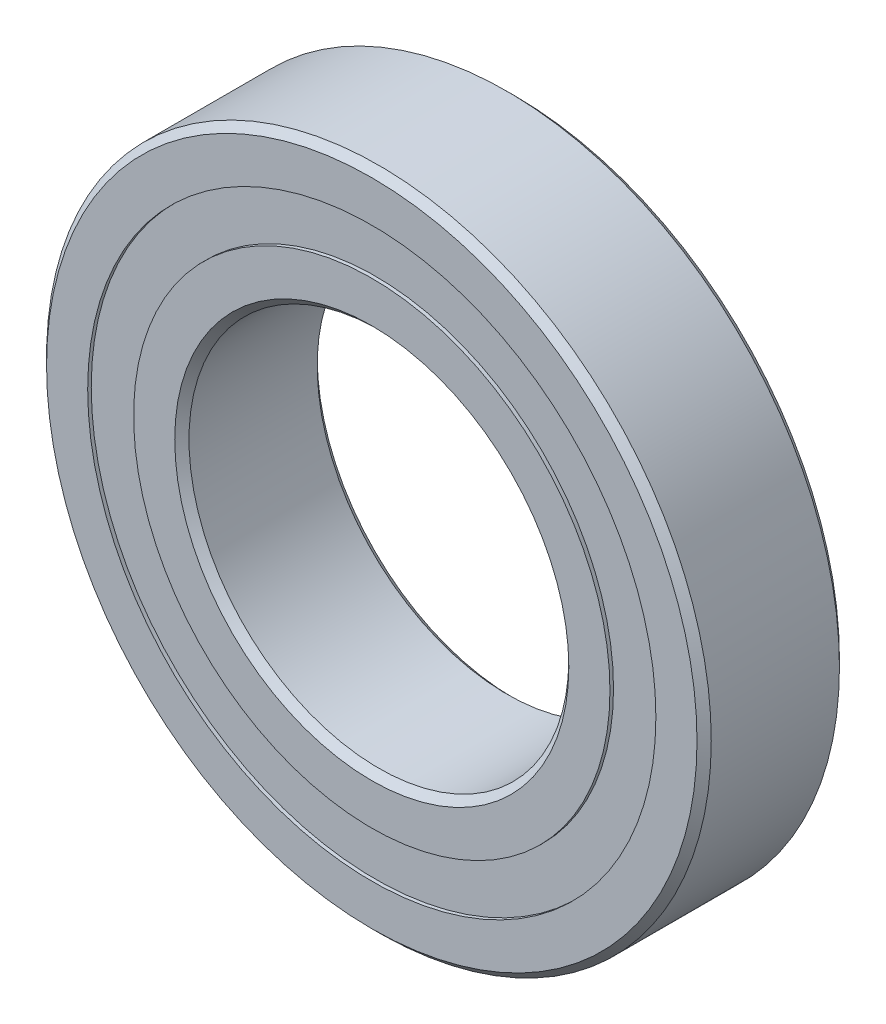
SolidWorks part; units mm, degrees
material "Alloy Steel (SS)"
ref_plane "Front Plane" through (0, 0, 0) normal (0, 0, 1) x (1, 0, 0)
ref_plane "Top Plane" through (0, 0, 0) normal (0, 1, 0) x (1, 0, 0)
ref_plane "Right Plane" through (0, 0, 0) normal (1, 0, 0) x (0, 0, -1)
sketch "Sketch1" plane through (0, 0, 0) normal (1, 0, 0) x (0, 0, -1)
  line L0 (-7.1437, 0) -> (7.1437, 0) construction
  line L1 (0, 33.3375) -> (0, -33.3375) construction
  line L2 (6.4294, 33.3375) -> (-6.4294, 33.3375)
  line L3 (-6.4294, 33.3375) -> (-7.1438, 32.6231)
  line L4 (-7.1438, 32.6231) -> (-7.1438, 28.4965)
  line L5 (-7.1438, 28.4965) -> (-3.175, 28.4965)
  line L6 (7.1438, 28.4965) -> (3.175, 28.4965)
  line L7 (7.1438, 32.6231) -> (7.1438, 28.4965)
  line L8 (6.4294, 33.3375) -> (7.1438, 32.6231)
  line L9 (0, 33.3375) -> (0, 26.1938) construction
  line L10 (0, 26.1938) -> (0, 19.05) construction
  arc A0 (-3.175, 28.4965) -> (3.175, 28.4965) centre (0, 26.1938) cw
  point P14 (0, 19.05)
  dimension "Width" = 14.2875
  dimension "OD" = 66.675
  dimension "D1" = 45
  dimension "D2" = 0.7144
  dimension "Shaft Dia" = 38.1
  dimension "D3" = 6.35
  dimension "D4" = 2.3027
revolve "Revolve1" add sketch "Sketch1" angle 360 about L0
sketch "Sketch3" plane through (0, 0, 0) normal (1, 0, 0) x (0, 0, -1)
  line L0 (-7.1438, 23.891) -> (-3.175, 23.891)
  line L1 (0, 33.3375) -> (0, -33.3375) construction
  line L2 (-7.1438, 32.6231) -> (-7.1438, 28.4965) construction
  line L3 (-7.1438, 23.891) -> (-7.1438, 19.7644)
  line L4 (-6.4294, 33.3375) -> (-7.1438, 32.6231) construction
  line L5 (-7.1438, 19.7644) -> (-6.4294, 19.05)
  line L6 (-6.4294, 19.05) -> (6.4294, 19.05)
  line L7 (6.4294, 33.3375) -> (6.4294, -33.3375) construction
  line L8 (6.4294, 19.05) -> (7.1438, 19.7644)
  line L9 (7.1438, -32.6231) -> (7.1438, 32.6231) construction
  line L10 (7.1438, 19.7644) -> (7.1438, 23.891)
  line L11 (7.1438, 23.891) -> (3.175, 23.891)
  line L13 (6.4294, 33.3375) -> (7.1438, 32.6231) construction
  arc A0 (3.175, 28.4965) -> (-3.175, 28.4965) centre (0, 26.1938) ccw construction
  arc A1 (3.175, 23.891) -> (-3.175, 23.891) centre (0, 26.1937) cw
revolve "Revolve3" add sketch "Sketch3" angle 360 about L0
sketch "Sketch4" plane through (0, 0, 0) normal (1, 0, 0) x (0, 0, -1)
  line L0 (-3.9222, 26.1938) -> (3.9222, 26.1938)
  arc A2 (-3.9222, 26.1938) -> (3.9222, 26.1938) centre (0, 26.1938) cw
  arc A3 (3.175, 28.4965) -> (-3.175, 28.4965) centre (0, 26.1938) ccw construction
revolve "Revolve4" add sketch "Sketch4" angle 360 about L0
ref_axis "Axis1" through (0, 0, -7.1437) along (0, 0, 1)
pattern_circular "CirPattern1" count 12 every 30 about axis through (0, 0, -7.1437) along (0, 0, 1) of bodies 104
sketch "Sketch5" plane through (0, 0, 0) normal (1, 0, 0) x (0, 0, -1)
  line L0 (-7.1438, 28.4965) -> (-3.175, 28.4965) construction
  line L1 (-6.7866, 28.4965) -> (-3.9222, 28.4965)
  line L2 (-6.7866, 28.4965) -> (-6.7866, 23.891)
  line L3 (-6.7866, 23.891) -> (-3.9222, 23.891)
  line L4 (-3.9222, 28.4965) -> (-3.9222, 23.891)
  line L5 (-7.1438, 23.891) -> (-3.175, 23.891) construction
  line L6 (7.1438, 28.4965) -> (3.175, 28.4965) construction
  line L7 (6.7866, 28.4965) -> (3.9222, 28.4965)
  line L8 (6.7866, 28.4965) -> (6.7866, 23.891)
  line L9 (6.7866, 23.891) -> (3.9222, 23.891)
  line L10 (3.9222, 28.4965) -> (3.9222, 23.891)
  line L11 (7.1438, 23.891) -> (3.175, 23.891) construction
  line L12 (-6.4294, 33.3375) -> (-7.1438, 32.6231) construction
  point P18 (-6.7866, 32.9803)
revolve "Revolve5" add sketch "Sketch5" angle 360 about L0
equation "\"D2@Sketch1\" = \"Width@Sketch1\"*.05"
equation "\"D3@Sketch1\" = \"Width@Sketch1\"/2.25"
equation "\"D4@Sketch1\" = (((\"OD@Sketch1\"-\"Width@Sketch1\")/2)/3.25)/3.5"
equation "\"D2@CirPattern1\" = 360/\"Balls@CirPattern1\""
